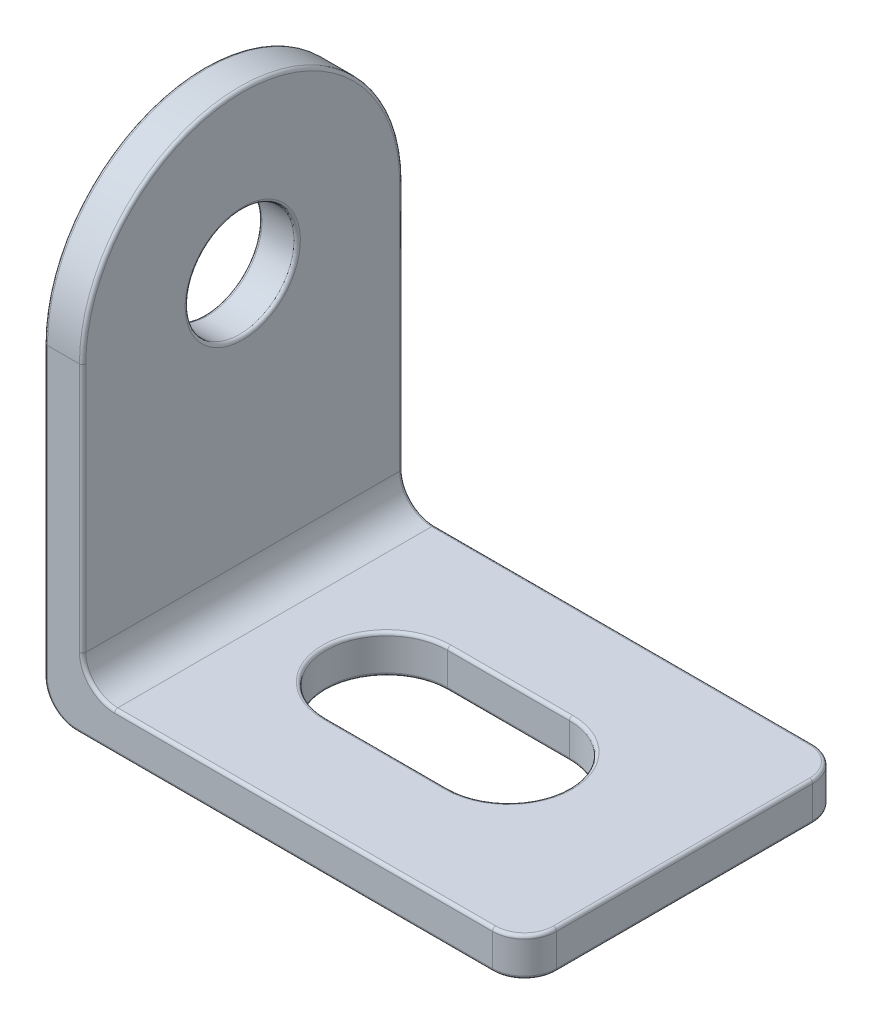
SolidWorks part; units mm, degrees
material "AISI 316 Stainless Steel Sheet (SS)"
ref_plane "Front Plane" through (0, 0, 0) normal (0, 0, 1) x (1, 0, 0)
ref_plane "Top Plane" through (0, 0, 0) normal (0, 1, 0) x (1, 0, 0)
ref_plane "Right Plane" through (0, 0, 0) normal (1, 0, 0) x (0, 0, -1)
sketch "Sketch1" plane through (0, 0, 0) normal (0, 0, 1) x (1, 0, 0)
  line L0 (0, 0) -> (0, 15)
  line L1 (0, 15) -> (1.2, 15)
  line L2 (1.2, 15) -> (1.2, 1.2)
  line L3 (1.2, 1.2) -> (15, 1.2)
  line L4 (15, 1.2) -> (15, 0)
  line L5 (15, 0) -> (0, 0)
  dimension "D1" = 15
  dimension "D2" = 15
  dimension "D3" = 1.2
extrude "Boss-Extrude1" add sketch "Sketch1" along normal blind 10
fillet "Fillet1" radius 1 2 edges at (0, 0, 5) (1.2, 1.2, 5)
sketch "Sketch2" plane through (1.2, 0, 0) normal (1, 0, 0) x (0, 0, -1)
  line L0 (-5, 2.2) -> (-5, 15) construction
  line L1 (-10, 2.2) -> (0, 2.2) construction
  line L2 (-10, 15) -> (0, 15) construction
  circle A0 centre (-5, 10) radius 1.7
  dimension "D1" = 5
  dimension "D2" = 3.4
extrude "Cut-Extrude1" cut sketch "Sketch2" against normal through all
ref_plane "Plane1" through (0, 0, 0) normal (-0.7071, 0.7071, 0) x (0.7071, 0.7071, 0)
sketch "Sketch3" plane through (1.2, 0, 0) normal (1, 0, 0) x (0, 0, -1)
  line L2 (-10, 15) -> (0, 15) construction
  line L3 (0, 0) -> (0, 1) construction
  line L4 (0, 10) -> (1, 10)
  line L5 (1, 10) -> (1, 16)
  line L6 (1, 16) -> (-11, 16)
  line L7 (-11, 16) -> (-11, 10)
  line L8 (-11, 10) -> (-10, 10)
  arc A0 (-10, 10) -> (0, 10) centre (-5, 10) cw
  circle A1 centre (-5, 10) radius 1.7 construction
  point P8 (-5, 15)
  dimension "D1" = 12
  dimension "D2" = 6
extrude "Cut-Extrude2" cut sketch "Sketch3" against normal through all
sketch "Sketch4" plane through (0, 1.2, 0) normal (0, 1, 0) x (1, 0, 0)
  line L0 (2.2, -5) -> (15, -5) construction
  line L1 (2.2, 0) -> (2.2, -10) construction
  line L2 (15, -10) -> (15, 0) construction
  line L3 (5.7, -5) -> (9.5, -5) construction
  line L4 (5.7, -3.1) -> (9.5, -3.1)
  line L5 (5.7, -6.9) -> (9.5, -6.9)
  arc A0 (5.7, -3.1) -> (5.7, -6.9) centre (5.7, -5) ccw
  arc A1 (9.5, -6.9) -> (9.5, -3.1) centre (9.5, -5) ccw
  point P8 (7.6, -5)
  dimension "D1" = 3.8
  dimension "D2" = 3.8
  dimension "D3" = 5.5
extrude "Cut-Extrude3" cut sketch "Sketch4" against normal through all
fillet "Fillet2" radius 0.1 26 edges at (8, 0, 0) (0.2929, 0.2929, 0) (8, 0, 10) (0.2929, 0.2929, 10) (1.4929, 1.4929, 10) (1.2, 6.1, 10) (1.2, 15, 5) (1.2, 6.1, 0) (1.4929, 1.4929, 0) (7.6, 0, 3.1) (11.4, 0, 5) (7.6, 0, 6.9) (15, 0, 5) (0, 5.5, 0) (0, 15, 5) (0, 5.5, 10) (0, 11.7, 5) (15, 1.2, 5) (8.6, 1.2, 10) (8.6, 1.2, 0) (11.4, 1.2, 5) (7.6, 1.2, 3.1) (3.8, 1.2, 5) (7.6, 1.2, 6.9) (3.8, 0, 5) (1.2, 11.7, 5)
fillet "Fillet3" radius 1 6 edges at (14.9707, 1.1707, 9.9707) (14.9707, 0.0293, 9.9707) (14.9707, 1.1707, 0.0293) (14.9707, 0.0293, 0.0293) (15, 0.6, 0) (15, 0.6, 10)
equation "\"length\"= 15"
equation "\"width\"= 15"
equation "\"depth\"= 10"
equation "\"D1@Sketch1\"=\"length\""
equation "\"D2@Sketch1\"=\"width\""
equation "\"thick\"= 1.2"
equation "\"D3@Sketch1\"=\"thick\""
equation "\"D1@Boss-Extrude1\"=\"depth\""
